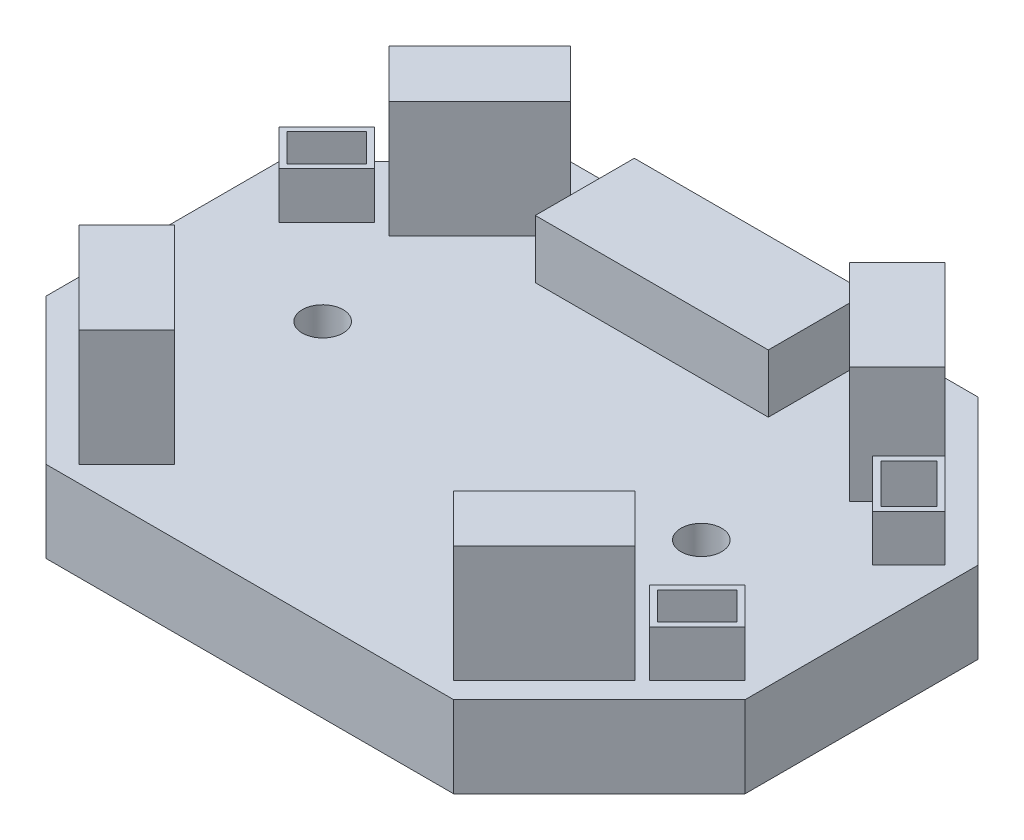
SolidWorks part; units mm, degrees
material "ABS"
ref_plane "前视基准面" through (0, 0, 0) normal (0, 0, 1) x (1, 0, 0)
ref_plane "上视基准面" through (0, 0, 0) normal (0, 1, 0) x (1, 0, 0)
ref_plane "右视基准面" through (0, 0, 0) normal (1, 0, 0) x (0, 0, -1)
sketch "草图1" plane through (0, 0, 0) normal (0, 1, 0) x (1, 0, 0)
  line L0 (0, 0) -> (35, 0)
  line L1 (35, 0) -> (47.5, -12.5)
  line L2 (47.5, -12.5) -> (47.5, -32.5)
  line L3 (47.5, -32.5) -> (35, -45)
  line L4 (35, -45) -> (0, -45)
  line L5 (0, -45) -> (-12.5, -32.5)
  line L6 (-12.5, -32.5) -> (-12.5, -12.5)
  line L7 (-12.5, -12.5) -> (0, 0)
  line L8 (17.5, 0) -> (17.5, -45) construction
  line L9 (47.5, -22.5) -> (-12.5, -22.5) construction
  line L10 (35, -45) -> (33.5858, -43.5858) construction
  line L11 (33.5858, -43.5858) -> (41.364, -35.8076)
  line L12 (41.364, -35.8076) -> (37.2627, -31.7064)
  line L13 (37.2627, -31.7064) -> (29.4846, -39.4846)
  line L14 (29.4846, -39.4846) -> (33.5858, -43.5858)
  line L15 (47.5, -32.5) -> (46.0858, -31.0858) construction
  line L16 (46.0858, -31.0858) -> (41.9846, -35.187)
  line L17 (41.9846, -35.187) -> (38.8733, -32.0757)
  line L18 (38.8733, -32.0757) -> (42.9745, -27.9745)
  line L19 (42.9745, -27.9745) -> (46.0858, -31.0858)
  line L20 (33.5858, -1.4142) -> (41.364, -9.1924)
  line L21 (29.4846, -5.5154) -> (33.5858, -1.4142)
  line L22 (41.364, -9.1924) -> (37.2627, -13.2936)
  line L23 (37.2627, -13.2936) -> (29.4846, -5.5154)
  line L24 (46.0858, -13.9142) -> (41.9846, -9.813)
  line L25 (41.9846, -9.813) -> (38.8733, -12.9243)
  line L26 (42.9745, -17.0255) -> (46.0858, -13.9142)
  line L27 (38.8733, -12.9243) -> (42.9745, -17.0255)
  line L28 (-7.9745, -17.0255) -> (-11.0858, -13.9142)
  line L29 (-3.8733, -12.9243) -> (-7.9745, -17.0255)
  line L30 (-11.0858, -13.9142) -> (-6.9846, -9.813)
  line L31 (-6.9846, -9.813) -> (-3.8733, -12.9243)
  line L32 (5.5154, -5.5154) -> (1.4142, -1.4142)
  line L33 (-6.364, -9.1924) -> (-2.2627, -13.2936)
  line L34 (1.4142, -1.4142) -> (-6.364, -9.1924)
  line L35 (-2.2627, -13.2936) -> (5.5154, -5.5154)
  line L36 (-11.0858, -31.0858) -> (-6.9846, -35.187)
  line L37 (-7.9745, -27.9745) -> (-11.0858, -31.0858)
  line L38 (-3.8733, -32.0757) -> (-7.9745, -27.9745)
  line L39 (-6.9846, -35.187) -> (-3.8733, -32.0757)
  line L40 (-6.364, -35.8076) -> (-2.2627, -31.7064)
  line L41 (1.4142, -43.5858) -> (-6.364, -35.8076)
  line L42 (5.5154, -39.4846) -> (1.4142, -43.5858)
  line L43 (-2.2627, -31.7064) -> (5.5154, -39.4846)
  line L45 (27.5, -2) -> (7.5, -2)
  line L46 (27.5, -2) -> (27.5, -10.5)
  line L47 (27.5, -10.5) -> (7.5, -10.5)
  line L48 (7.5, -2) -> (7.5, -10.5)
  line L49 (27.5, -2) -> (7.5, -10.5) construction
  line L50 (27.5, -10.5) -> (7.5, -2) construction
  circle A0 centre (33.75, -22.5) radius 1.75
  circle A1 centre (1.25, -22.5) radius 1.75
  point P15 (35.5, -22.5)
  point P30 (17.5, -6.25)
  dimension "D5" = 3.5
  dimension "D1" = 60
  dimension "D2" = 45
  dimension "D3" = 20
  dimension "D4" = 35
  dimension "D6" = 12
  dimension "D7" = 2
  dimension "D8" = 5.8
  dimension "D9" = 11
  dimension "D10" = 2
  dimension "D11" = 4.4
  dimension "D12" = 5.8
  dimension "D13" = 20
  dimension "D14" = 8.5
  dimension "D15" = 2
extrude "凸台-拉伸1" add sketch "草图1" along normal blind 7
extrude "凸台-拉伸2" add sketch "草图1<2>" along normal blind 17 contours L23 L22 L20 L21 | L33 L35 L32 L34 | L43 L40 L41 L42 | L13 L14 L11 L12 region at (35.4243, 0, 37.6461) region at (35.4243, 0, 7.3539) region at (-0.4243, 0, 7.3539) region at (-0.4243, 0, 37.6461)
sketch "草图1<2>" plane through (0, 0, 0) normal (0, 1, 0) x (1, 0, 0) same geometry as "草图1"
extrude "凸台-拉伸3" add sketch "草图1<3>" along normal blind 11 contours L36 L39 L38 L37 | L19 L18 L17 L16 | L25 L27 L26 L24 | L31 L30 L28 L29 region at (42.4795, 0, 31.5808) region at (42.4795, 0, 13.4192) region at (-7.4795, 0, 13.4192) region at (-7.4795, 0, 31.5808)
sketch "草图1<3>" plane through (0, 0, 0) normal (0, 1, 0) x (1, 0, 0) same geometry as "草图1"
extrude "凸台-拉伸4" add sketch "草图1<4>" along normal blind 12 contours L45 L48 L47 L46 region at (17.5, 0, 6.25)
sketch "草图1<4>" plane through (0, 0, 0) normal (0, 1, 0) x (1, 0, 0) same geometry as "草图1"
shell "抽壳4" thickness 0.5 removed face at (17.5, 9.5, 2) removed face at (42.4795, 11, 31.5808) removed face at (42.4795, 11, 13.4192) removed face at (-7.4795, 11, 13.4192) removed face at (-7.4795, 11, 31.5808)
